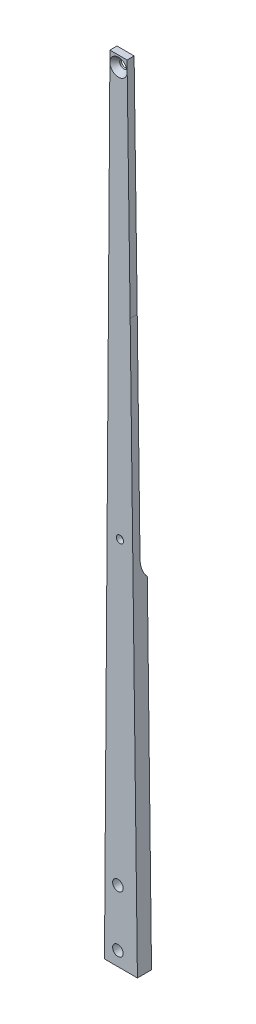
SolidWorks part; units mm, degrees
ref_plane "XY" through (0, 0, 0) normal (0, 0, 1) x (1, 0, 0)
ref_plane "XZ" through (0, 0, 0) normal (0, 1, 0) x (1, 0, 0)
ref_plane "YZ" through (0, 0, 0) normal (1, 0, 0) x (0, 0, -1)
ref_axis "X" through (-4.8636, 0, 0) along (1, 0, 0)
ref_axis "Y" through (0, -19.9998, 0) along (0, 1, 0)
ref_axis "Z" through (0, 0, 6.7699) along (0, 0, -1)
sketch "Sketch3" plane through (0, 0, 0) normal (0, 0, 1) x (1, 0, 0)
  line B0 (6.1442, 399.996) -> (-1.5646, 399.996)
  arc B1 (10.9787, 29.7914) -> (-4.1092, 31.483) centre (0, 0) ccw
  spline B2 degree 3 poles (-2.2314, 299.996) (-2.2349, 299.49) (-2.393, 276.4245) (-2.5531, 253.359) (-2.8683, 208.24) (-3.0269, 185.6805) (-3.3464, 140.3) (-3.6556, 96.4207) (-3.9627, 52.5413) (-4.1092, 31.483) knots 0 0 0 0 0.005653 0.257702 0.257702 0.509751 0.509751 0.764723 1 1 1 1
  spline B3 degree 3 poles (-1.5646, 399.996) (-1.6372, 388.7162) (-1.7108, 377.4364) (-1.931, 344.1246) (-2.0802, 322.0711) (-2.2313, 300.0175) (-2.2314, 299.996) knots 0 0 0 0 0.338393 0.338393 0.999354 1 1 1 1
  spline B4 degree 3 poles (7.5462, 299.996) (7.092, 333.3295) (6.6238, 366.6628) (6.1442, 399.996) knots 0 0 0 0 1 1 1 1
  spline B5 degree 3 poles (10.9787, 29.7914) (9.9109, 119.8606) (8.7733, 209.9289) (7.5462, 299.996) knots 0 0 0 0 1 1 1 1
sketch_block_instance "Block-RearSpar-1"
sketch_block "Block-RearSpar"
sketch "Sketch4" plane through (0, 0, 0) normal (0, 0, 1) x (1, 0, 0)
  line L2 (6.1442, 399.996) -> (-1.5646, 399.996) construction
  line L3 (6.1442, 399.996) -> (-1.5646, 399.996)
  arc A0 (10.9787, 29.7914) -> (-4.1092, 31.483) centre (0, 0) ccw construction
  arc A1 (10.9787, 29.7914) -> (-4.1092, 31.483) centre (0, 0) ccw
  spline S2 degree 3 poles (-121.6535, 2293.9975) (5.1575, 1627.3849) (2.2169, 940.3657) (-2.5531, 253.359) (-2.8683, 208.24) (-3.0269, 185.6805) (-3.3464, 140.3) (-8.3535, -570.1873) (-12.8071, -1280.6785) (-1.472, -1968.4561) knots -7.417974 -7.417974 -7.417974 -7.417974 0.005653 0.257702 0.257702 0.509751 0.509751 0.764723 8.447775 8.447775 8.447775 8.447775 only from (-2.2314, 299.996) to (-4.1092, 31.483) construction
  spline S3 degree 3 poles (-46.2092, 2399.0845) (3.9416, 1721.255) (2.6931, 1043.695) (-1.931, 344.1246) (-5.1261, -128.2574) (-9.209, -600.6333) (-435.2561, -1640.5057) knots -19.987749 -19.987749 -19.987749 -19.987749 0.338393 0.338393 0.999354 14.509863 14.509863 14.509863 14.509863 only from (-1.5646, 399.996) to (-2.2314, 299.996) construction
  spline S4 degree 3 poles (-2.9312, -1699.8175) (44.279, -332.5444) (-19.8869, 1033.1673) (-15.4341, 2399.841) knots -19.992737 -19.992737 -19.992737 -19.992737 20.997545 20.997545 20.997545 20.997545 only from (7.5462, 299.996) to (6.1442, 399.996) construction
  spline S5 degree 3 poles (31.3042, -1970.0909) (13.5099, -546.9668) (15.0768, 876.6883) (-42.477, 2299.3052) knots -7.401386 -7.401386 -7.401386 -7.401386 8.400667 8.400667 8.400667 8.400667 only from (10.9787, 29.7914) to (7.5462, 299.996) construction
  spline S6 degree 3 poles (-2.2314, 299.996) (-2.2349, 299.49) (-2.393, 276.4245) (-2.5531, 253.359) (-2.8683, 208.24) (-3.0269, 185.6805) (-3.3464, 140.3) (-3.6556, 96.4207) (-3.9627, 52.5413) (-4.1092, 31.483) knots 0 0 0 0 0.005653 0.257702 0.257702 0.509751 0.509751 0.764723 1 1 1 1
  spline S7 degree 3 poles (-1.5646, 399.996) (-1.6372, 388.7162) (-1.7108, 377.4364) (-1.931, 344.1246) (-2.0802, 322.0711) (-2.2313, 300.0175) (-2.2314, 299.996) knots 0 0 0 0 0.338393 0.338393 0.999354 1 1 1 1
  spline S8 degree 3 poles (7.5462, 299.996) (7.092, 333.3295) (6.6238, 366.6628) (6.1442, 399.996) knots 0 0 0 0 1 1 1 1
  spline S9 degree 3 poles (10.9787, 29.7914) (9.9109, 119.8606) (8.7733, 209.9289) (7.5462, 299.996) knots 0 0 0 0 1 1 1 1
extrude "Boss-Extrude2" add sketch "Sketch4" along normal blind 6.35
sketch "Sketch5" plane through (0, 0, 0) normal (0, 0, 1) x (1, 0, 0)
  line L0 (0, 44.45) -> (0, 0) construction
  line L1 (-12.7, 0) -> (12.7, 0)
  line L2 (-12.7, 0) -> (-12.7, 44.45)
  line L4 (12.7, 0) -> (12.7, 44.45)
  line L13 (12.7, 44.45) -> (-12.7, 44.45)
  circle A1 centre (0, 0) radius 31.75 construction
  dimension "D1" = 25.4
  dimension "D2" = 44.45
extrude "Cut-Extrude1" cut sketch "Sketch5" along normal through all
hole_wizard "3/16 (0.1875) Dowel Hole1" positions "Sketch7" profile "Sketch8" hole size "3/16" standard "ANSI Inch"
sketch "Sketch7" plane through (0, 0, 6.35) normal (0, 0, 1) x (1, 0, 0)
  line L0 (2.032, 76.2) -> (2.032, 50.8) construction
  line L1 (2.032, 50.8) -> (2.032, 44.45) construction
  line L3 (10.8043, 44.45) -> (-4.0189, 44.45) construction
  line L4 (2.032, 44.45) -> (0, 0)
  point P0 (2.032, 50.8)
  point P2 (2.032, 76.2)
  dimension "D1" = 25.4
  dimension "D2" = 6.35
  dimension "D3" = 2.032
sketch "Sketch8" plane through (2.032, 50.8, 6.35) normal (1, 0, 0) x (0, -1, 0)
  line L0 (0, 0) -> (0, 12.0988)
  line L1 (0, 12.0988) -> (2.3812, 10.668)
  line L2 (2.3812, 10.668) -> (2.3812, 0)
  line L5 (2.3812, 0) -> (0, 0)
  line L10 (0, 12.0988) -> (-2.3813, 10.668) construction
  line L11 (0, -6.35) -> (0, 107.95) construction
  dimension "Hole Dia." = 4.7625
  dimension "Hole Depth" = 10.668
  dimension "Drill Angle" = 118
hole_wizard "CSK for #6 Flat Head Socket Cap Screw1" positions "Sketch10" profile "Sketch11" countersink size "#6" standard "ANSI Inch" end condition through all
sketch "Sketch10" plane through (0, 0, 6.35) normal (0, 0, -1) x (-1, 0, 0)
  line L0 (-2.2898, 399.996) -> (-2.2898, 395.2335)
  line L1 (-6.1442, 399.996) -> (1.5646, 399.996) construction
  point P2 (-2.2898, 395.2335)
  dimension "D1" = 4.7625
sketch "Sketch11" plane through (2.2898, 395.2335, 6.35) normal (1, 0, 0) x (0, -1, 0)
  line L0 (0, 0) -> (0, 6.35)
  line L1 (0, 6.35) -> (1.8288, 6.35)
  line L2 (1.8288, 6.35) -> (1.8288, 2.3814)
  line L3 (1.8288, 2.3814) -> (3.8989, 0)
  line L5 (3.8989, 0) -> (0, 0)
  line L6 (-1.8288, 2.3814) -> (-3.8989, 0) construction
  line L11 (0, -6.35) -> (0, 107.95) construction
  dimension "Thru Hole Dia." = 3.6576
  dimension "Thru Hole Depth" = 6.35
  dimension "Near C'Sink Dia." = 7.7978
  dimension "Near C'Sink Angle" = 82
sketch "Sketch12" plane through (0, 0, 0) normal (0, 0, -1) x (-1, 0, 0)
  line L0 (-6.1442, 399.996) -> (1.5646, 399.996) construction
  line L1 (13.3747, 196.796) -> (-18.6195, 196.796)
  line L2 (13.3747, 196.796) -> (13.3747, 399.996)
  line L3 (13.3747, 399.996) -> (-18.6195, 399.996)
  line L4 (-18.6195, 196.796) -> (-18.6195, 399.996)
  dimension "D1" = 203.2
extrude "Cut-Extrude2" cut sketch "Sketch12" against normal blind 3.175
fillet "Fillet1" radius 12.7 1 edges at (2.9826, 196.796, 3.175)
hole_wizard "CSK for #4 Flat Head Machine Screw (100)1" positions "Sketch13" profile "Sketch14" countersink size "#4" standard "ANSI Inch" end condition through all
sketch "Sketch13" plane through (0, 0, 3.175) normal (0, 0, -1) x (-1, 0, 0)
  line L0 (-2.9578, 205.1963) -> (-2.2898, 399.996) construction
  line L1 (-8.8056, 205.1963) -> (2.89, 205.1963) construction
  line L2 (1.5646, 399.996) -> (-6.1442, 399.996) construction
  point P0 (-2.936, 211.5463)
  dimension "D1" = 6.35
sketch "Sketch14" plane through (2.936, 211.5463, 3.175) normal (1, 0, 0) x (0, 1, 0)
  line L0 (0, 0) -> (0, 3.175)
  line L1 (0, 3.175) -> (1.6319, 3.175)
  line L2 (1.6319, 3.175) -> (1.6319, 1.0284)
  line L3 (1.6319, 1.0284) -> (2.8575, 0)
  line L5 (2.8575, 0) -> (0, 0)
  line L6 (-1.6319, 1.0284) -> (-2.8575, 0) construction
  line L11 (0, -6.35) -> (0, 107.95) construction
  dimension "Thru Hole Dia." = 3.2639
  dimension "Thru Hole Depth" = 3.175
  dimension "Near C'Sink Dia." = 5.715
  dimension "Near C'Sink Angle" = 100
